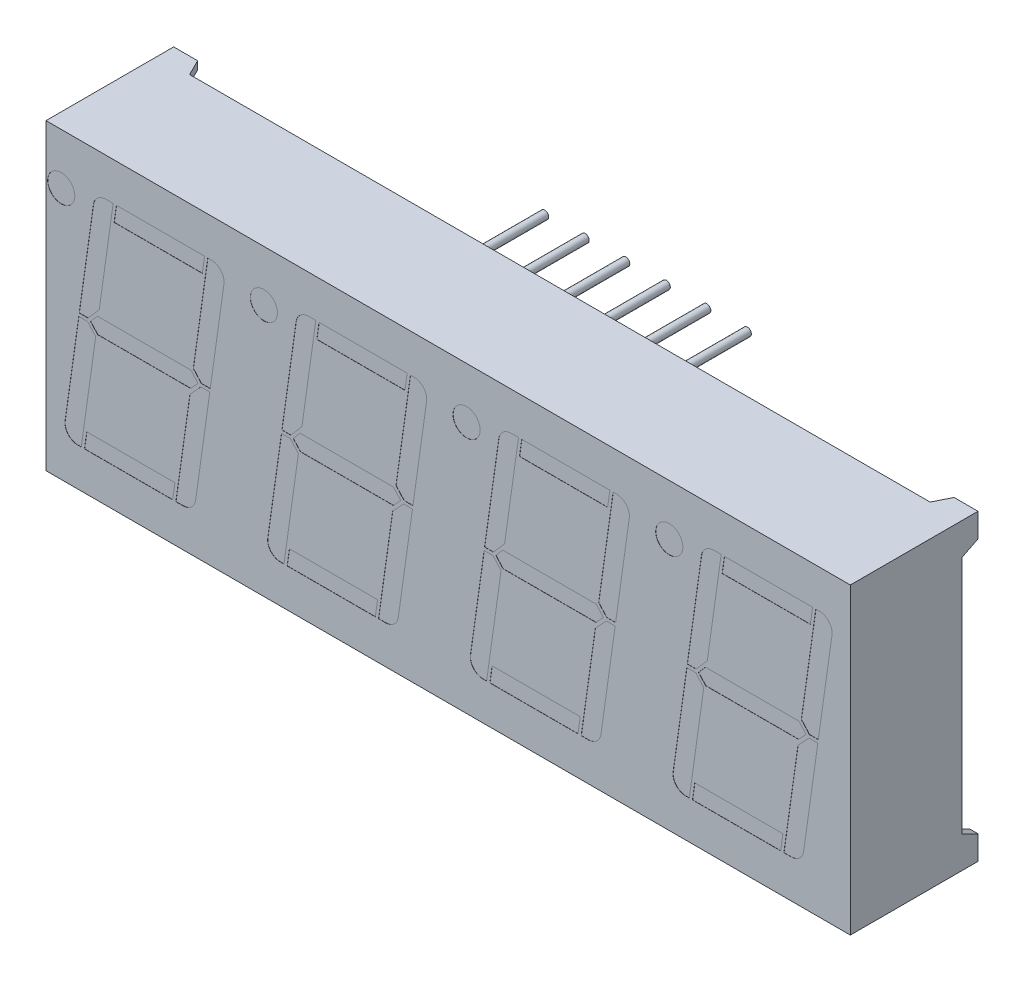
SolidWorks part; units mm, degrees
ref_plane "Front Plane" through (0, 0, 0) normal (0, 0, 1) x (1, 0, 0)
ref_plane "Top Plane" through (0, 0, 0) normal (0, 1, 0) x (1, 0, 0)
ref_plane "Right Plane" through (0, 0, 0) normal (1, 0, 0) x (0, 0, -1)
sketch "Sketch1" plane through (0, 0, 0) normal (0, 1, 0) x (1, 0, 0)
  line L1 (0, 0) -> (50.4, 0)
  line L2 (0, 0) -> (0, 8)
  line L3 (0, 8) -> (50.4, 8)
  line L4 (50.4, 0) -> (50.4, 8)
  dimension "D1" = 8
  dimension "D2" = 50.4
extrude "body" add sketch "Sketch1" along normal blind 19
sketch "Sketch2" plane through (0, 0, -8) normal (0, 0, -1) x (-1, 0, 0)
  line L0 (-50.4, 17) -> (-49.9, 17)
  line L1 (-50.4, 19) -> (-50.4, 0) construction
  line L2 (-49.9, 17) -> (-49.9, 18.5)
  line L3 (-49.9, 18.5) -> (-48.4, 18.5)
  line L4 (-48.4, 18.5) -> (-48.4, 19)
  line L5 (-50.4, 19) -> (0, 19) construction
  line L6 (-48.4, 19) -> (-2, 19)
  line L7 (-2, 19) -> (-2, 18.5)
  line L8 (-2, 18.5) -> (-0.5, 18.5)
  line L9 (-0.5, 18.5) -> (-0.5, 17)
  line L10 (-0.5, 17) -> (0, 17)
  line L11 (0, 19) -> (0, 0) construction
  line L12 (0, 17) -> (0, 2)
  line L13 (0, 2) -> (-0.5, 2)
  line L14 (-0.5, 2) -> (-0.5, 0.5)
  line L15 (-0.5, 0.5) -> (-2, 0.5)
  line L16 (-2, 0.5) -> (-2, 0)
  line L17 (-50.4, 0) -> (0, 0) construction
  line L18 (-2, 0) -> (-48.4, 0)
  line L19 (-48.4, 0) -> (-48.4, 0.5)
  line L20 (-48.4, 0.5) -> (-49.9, 0.5)
  line L21 (-49.9, 0.5) -> (-49.9, 2)
  line L22 (-49.9, 2) -> (-50.4, 2)
  line L23 (-50.4, 2) -> (-50.4, 17)
  line L24 (-49.9, 17) -> (-49.9, 2) construction
  line L25 (-48.4, 0.5) -> (-2, 0.5) construction
  line L26 (-0.5, 2) -> (-0.5, 17) construction
  line L27 (-2, 18.5) -> (-48.4, 18.5) construction
  line L28 (-2, 0.5) -> (-2, 18.5) construction
  line L29 (-0.5, 17) -> (-49.9, 17) construction
  line L30 (-48.4, 0.5) -> (-48.4, 18.5) construction
  line L31 (-49.9, 2) -> (-0.5, 2) construction
  dimension "D1" = 0.5
  dimension "D2" = 2
  dimension "D3" = 2
  dimension "D4" = 2
  dimension "D5" = 2
extrude "backLegs" cut sketch "Sketch2" against normal blind 1
chamfer "backLegsChamfer" distance 0.5 distance2 1 8 edges at (50.15, 2, -8) (48.4, 0.25, -8) (2, 0.25, -8) (0.25, 2, -8) (2, 18.75, -8) (0.25, 17, -8) (48.4, 18.75, -8) (50.15, 17, -8) first distance on face at (49.5667, 0.8333, -8) first distance on face at (0.8333, 0.8333, -8) first distance on face at (0.8333, 18.1667, -8) first distance on face at (49.5667, 18.1667, -8)
sketch "Sketch3" plane through (0, 0, -7) normal (0, 0, -1) x (-1, 0, 0)
  line L21 (-49.9, 0.5) -> (-0.5, 0.5)
  line L22 (-49.9, 0.5) -> (-49.9, 18.5)
  line L23 (-49.9, 18.5) -> (-0.5, 18.5)
  line L24 (-0.5, 0.5) -> (-0.5, 18.5)
extrude "backCut" cut sketch "Sketch3" against normal blind 0.1
sketch "Sketch4" plane through (0, 0, -6.9) normal (0, 0, -1) x (-1, 0, 0)
  line L0 (-49.9, 9.5) -> (-0.5, 9.5) construction
  line L1 (-49.9, 2) -> (-49.9, 17) construction
  line L2 (-0.5, 0.5) -> (-0.5, 18.5) construction
  line L3 (-49.9, 17.12) -> (-0.5, 17.12) construction
  line L4 (-49.9, 18.5) -> (-49.9, 0.5) construction
  line L5 (-0.5, 1.88) -> (-49.9, 1.88) construction
  line L6 (-25.2, 1.88) -> (-25.2, 17.12) construction
  line L7 (-26.47, 17.12) -> (-25.2, 15.85) construction
  line L8 (-25.2, 15.85) -> (-23.93, 17.12) construction
  line L9 (-31.55, 17.12) -> (-31.55, 1.88) construction
  line L10 (-29.01, 17.12) -> (-29.01, 1.88) construction
  line L11 (-26.47, 17.12) -> (-26.47, 1.88) construction
  line L12 (-23.93, 17.12) -> (-23.93, 1.88) construction
  line L13 (-21.39, 17.12) -> (-21.39, 1.88) construction
  line L14 (-18.85, 17.12) -> (-18.85, 1.88) construction
  circle A0 centre (-31.55, 17.12) radius 0.25
  circle A1 centre (-29.01, 17.12) radius 0.25
  circle A2 centre (-26.47, 17.12) radius 0.25
  circle A3 centre (-23.93, 17.12) radius 0.25
  circle A4 centre (-21.39, 17.12) radius 0.25
  circle A5 centre (-18.85, 17.12) radius 0.25
  circle A6 centre (-31.55, 1.88) radius 0.25
  circle A7 centre (-29.01, 1.88) radius 0.25
  circle A8 centre (-26.47, 1.88) radius 0.25
  circle A10 centre (-23.93, 1.88) radius 0.25
  circle A11 centre (-21.39, 1.88) radius 0.25
  circle A12 centre (-18.85, 1.88) radius 0.25
  point P30 (-25.2, 9.5)
  dimension "D6" = 0.5
  dimension "D1" = 15.24
  dimension "D2" = 2.54
  dimension "D3" = 2.54
  dimension "D4" = 2.54
  dimension "D5" = 2.54
  dimension "D7" = 2.54
  dimension "D8" = 45
  dimension "D9" = 45
extrude "pins" add sketch "Sketch4" along normal blind 5.5
sketch "Sketch5" plane through (0, 0, 0) normal (0, 0, 1) x (1, 0, 0)
  line L0 (0, 9.5) -> (50.4, 9.5) construction
  line L1 (0, 19) -> (0, 0) construction
  line L2 (50.4, 19) -> (50.4, 0) construction
  line L3 (49.2488, 15.6987) -> (48.3916, 9.6)
  line L4 (0, 19) -> (50.4, 19) construction
  line L5 (0, 0) -> (50.4, 0) construction
  line L6 (6.15, 19) -> (6.15, 0) construction
  line L7 (18.85, 0) -> (18.85, 19) construction
  line L8 (31.55, 0) -> (31.55, 19) construction
  line L9 (44.25, 0) -> (44.25, 19) construction
  line L10 (25.2, 9.5) -> (25.2, 19) construction
  line L11 (25.2, 14.25) -> (18.85, 14.25) construction
  line L12 (25.2, 14.25) -> (31.55, 14.25) construction
  line L13 (50.4, 16.61) -> (0, 16.61) construction
  line L14 (50.4, 2.39) -> (0, 2.39) construction
  line L15 (49.4, 16.61) -> (49.4, 9.5) construction
  line L16 (49.4, 9.5) -> (49.4, 2.39) construction
  line L17 (48.3916, 9.6) -> (47.8362, 9.6)
  line L18 (47.8362, 9.6) -> (47.3296, 10.1627)
  line L19 (47.3296, 10.1627) -> (48.2357, 16.61)
  line L20 (48.3916, 9.6) -> (48.3635, 9.4) construction
  line L21 (48.3635, 9.4) -> (47.4751, 3.0787)
  line L22 (48.3635, 9.4) -> (47.8081, 9.4)
  line L23 (47.8081, 9.4) -> (47.1185, 8.6605)
  line L24 (47.1185, 8.6605) -> (46.2372, 2.39)
  line L25 (47.6279, 9.5) -> (47.1617, 9)
  line L26 (47.1617, 9) -> (41.3383, 9)
  line L27 (41.3383, 9) -> (40.8881, 9.5)
  line L28 (40.8881, 9.5) -> (41.3223, 10)
  line L29 (41.3223, 10) -> (47.1777, 10)
  line L30 (47.1777, 10) -> (47.6279, 9.5)
  line L31 (44.25, 9) -> (44.25, 10) construction
  line L32 (47.8081, 9.4) -> (47.8362, 9.6) construction
  line L33 (40.709, 9.4) -> (40.7372, 9.6) construction
  line L34 (46.2372, 2.39) -> (46.6829, 2.39)
  line L35 (46.0353, 2.39) -> (46.1758, 3.39)
  line L36 (46.1758, 3.39) -> (40.6521, 3.39)
  line L37 (40.6521, 3.39) -> (40.5115, 2.39)
  line L38 (40.5115, 2.39) -> (46.0353, 2.39)
  line L39 (43.4139, 3.39) -> (43.4139, 2.39) construction
  line L43 (40.1536, 9.4) -> (39.2965, 3.3013)
  line L44 (40.1536, 9.4) -> (40.1818, 9.6) construction
  line L45 (47.3296, 10.1627) -> (47.1185, 8.6605) construction
  line L46 (40.3096, 2.39) -> (41.2157, 8.8373)
  line L47 (40.1818, 9.6) -> (41.0702, 15.9213)
  line L48 (41.436, 10.4048) -> (42.308, 16.61)
  line L49 (41.2157, 8.8373) -> (41.436, 10.4048) construction
  line L50 (41.436, 10.4048) -> (40.7372, 9.6)
  line L51 (40.7372, 9.6) -> (40.1818, 9.6)
  line L52 (44.25, 9.5) -> (44.2005, 9.4505) construction
  line L53 (36.5488, 15.6987) -> (35.6916, 9.6)
  line L54 (41.2157, 8.8373) -> (40.709, 9.4)
  line L55 (40.709, 9.4) -> (40.1536, 9.4)
  line L56 (40.3096, 2.39) -> (40.0887, 2.39)
  line L57 (42.308, 16.61) -> (41.8624, 16.61)
  line L58 (48.2357, 16.61) -> (48.4565, 16.61)
  line L59 (46.1758, 3.39) -> (47.8932, 15.61) construction
  line L60 (40.6521, 3.39) -> (42.3695, 15.61) construction
  line L61 (47.8932, 15.61) -> (42.3695, 15.61)
  line L62 (42.3695, 15.61) -> (42.51, 16.61)
  line L63 (47.8932, 15.61) -> (48.0338, 16.61)
  line L64 (48.0338, 16.61) -> (42.51, 16.61)
  line L65 (35.6916, 9.6) -> (35.1362, 9.6)
  line L66 (35.1362, 9.6) -> (34.6296, 10.1627)
  line L67 (34.6296, 10.1627) -> (35.5357, 16.61)
  line L68 (35.6635, 9.4) -> (34.7751, 3.0787)
  line L69 (35.6635, 9.4) -> (35.1081, 9.4)
  line L70 (35.1081, 9.4) -> (34.4185, 8.6605)
  line L71 (34.4185, 8.6605) -> (33.5372, 2.39)
  line L72 (34.9279, 9.5) -> (34.4617, 9)
  line L73 (34.4617, 9) -> (28.6383, 9)
  line L74 (28.6383, 9) -> (28.1881, 9.5)
  line L75 (28.1881, 9.5) -> (28.6223, 10)
  line L76 (28.6223, 10) -> (34.4777, 10)
  line L77 (34.4777, 10) -> (34.9279, 9.5)
  line L78 (33.5372, 2.39) -> (33.9829, 2.39)
  line L79 (33.3353, 2.39) -> (33.4758, 3.39)
  line L80 (33.4758, 3.39) -> (27.9521, 3.39)
  line L81 (27.9521, 3.39) -> (27.8115, 2.39)
  line L82 (27.8115, 2.39) -> (33.3353, 2.39)
  line L83 (27.4536, 9.4) -> (26.5965, 3.3013)
  line L84 (27.6096, 2.39) -> (28.5157, 8.8373)
  line L85 (27.4818, 9.6) -> (28.3702, 15.9213)
  line L86 (28.736, 10.4048) -> (29.608, 16.61)
  line L87 (28.736, 10.4048) -> (28.0372, 9.6)
  line L88 (28.0372, 9.6) -> (27.4818, 9.6)
  line L89 (28.5157, 8.8373) -> (28.009, 9.4)
  line L90 (28.009, 9.4) -> (27.4536, 9.4)
  line L91 (27.6096, 2.39) -> (27.3887, 2.39)
  line L92 (29.608, 16.61) -> (29.1624, 16.61)
  line L93 (35.5357, 16.61) -> (35.7565, 16.61)
  line L94 (35.1932, 15.61) -> (29.6695, 15.61)
  line L95 (29.6695, 15.61) -> (29.81, 16.61)
  line L96 (35.1932, 15.61) -> (35.3338, 16.61)
  line L97 (35.3338, 16.61) -> (29.81, 16.61)
  line L98 (35.6916, 9.6) -> (35.6635, 9.4) construction
  line L99 (31.55, 9) -> (31.55, 10) construction
  line L100 (35.1081, 9.4) -> (35.1362, 9.6) construction
  line L101 (28.009, 9.4) -> (28.0372, 9.6) construction
  line L102 (30.7139, 3.39) -> (30.7139, 2.39) construction
  line L103 (27.4536, 9.4) -> (27.4818, 9.6) construction
  line L104 (34.6296, 10.1627) -> (34.4185, 8.6605) construction
  line L105 (28.5157, 8.8373) -> (28.736, 10.4048) construction
  line L106 (31.55, 9.5) -> (31.5005, 9.4505) construction
  line L107 (33.4758, 3.39) -> (35.1932, 15.61) construction
  line L108 (27.9521, 3.39) -> (29.6695, 15.61) construction
  line L109 (23.8488, 15.6987) -> (22.9916, 9.6)
  line L110 (22.9916, 9.6) -> (22.4362, 9.6)
  line L111 (22.4362, 9.6) -> (21.9296, 10.1627)
  line L112 (21.9296, 10.1627) -> (22.8357, 16.61)
  line L113 (22.9635, 9.4) -> (22.0751, 3.0787)
  line L114 (22.9635, 9.4) -> (22.4081, 9.4)
  line L115 (22.4081, 9.4) -> (21.7185, 8.6605)
  line L116 (21.7185, 8.6605) -> (20.8372, 2.39)
  line L117 (22.2279, 9.5) -> (21.7617, 9)
  line L118 (21.7617, 9) -> (15.9383, 9)
  line L119 (15.9383, 9) -> (15.4881, 9.5)
  line L120 (15.4881, 9.5) -> (15.9223, 10)
  line L121 (15.9223, 10) -> (21.7777, 10)
  line L122 (21.7777, 10) -> (22.2279, 9.5)
  line L123 (20.8372, 2.39) -> (21.2829, 2.39)
  line L124 (20.6353, 2.39) -> (20.7758, 3.39)
  line L125 (20.7758, 3.39) -> (15.2521, 3.39)
  line L126 (15.2521, 3.39) -> (15.1115, 2.39)
  line L127 (15.1115, 2.39) -> (20.6353, 2.39)
  line L128 (14.7536, 9.4) -> (13.8965, 3.3013)
  line L129 (14.9096, 2.39) -> (15.8157, 8.8373)
  line L130 (14.7818, 9.6) -> (15.6702, 15.9213)
  line L131 (16.036, 10.4048) -> (16.908, 16.61)
  line L132 (16.036, 10.4048) -> (15.3372, 9.6)
  line L133 (15.3372, 9.6) -> (14.7818, 9.6)
  line L134 (15.8157, 8.8373) -> (15.309, 9.4)
  line L135 (15.309, 9.4) -> (14.7536, 9.4)
  line L136 (14.9096, 2.39) -> (14.6887, 2.39)
  line L137 (16.908, 16.61) -> (16.4624, 16.61)
  line L138 (22.8357, 16.61) -> (23.0565, 16.61)
  line L139 (22.4932, 15.61) -> (16.9695, 15.61)
  line L140 (16.9695, 15.61) -> (17.11, 16.61)
  line L141 (22.4932, 15.61) -> (22.6338, 16.61)
  line L142 (22.6338, 16.61) -> (17.11, 16.61)
  line L143 (22.9916, 9.6) -> (22.9635, 9.4) construction
  line L144 (18.85, 9) -> (18.85, 10) construction
  line L145 (22.4081, 9.4) -> (22.4362, 9.6) construction
  line L146 (15.309, 9.4) -> (15.3372, 9.6) construction
  line L147 (18.0139, 3.39) -> (18.0139, 2.39) construction
  line L148 (14.7536, 9.4) -> (14.7818, 9.6) construction
  line L149 (21.9296, 10.1627) -> (21.7185, 8.6605) construction
  line L150 (15.8157, 8.8373) -> (16.036, 10.4048) construction
  line L151 (18.85, 9.5) -> (18.8005, 9.4505) construction
  line L152 (20.7758, 3.39) -> (22.4932, 15.61) construction
  line L153 (15.2521, 3.39) -> (16.9695, 15.61) construction
  line L154 (11.1488, 15.6987) -> (10.2916, 9.6)
  line L155 (10.2916, 9.6) -> (9.7362, 9.6)
  line L156 (9.7362, 9.6) -> (9.2296, 10.1627)
  line L157 (9.2296, 10.1627) -> (10.1357, 16.61)
  line L158 (10.2635, 9.4) -> (9.3751, 3.0787)
  line L159 (10.2635, 9.4) -> (9.7081, 9.4)
  line L160 (9.7081, 9.4) -> (9.0185, 8.6605)
  line L161 (9.0185, 8.6605) -> (8.1372, 2.39)
  line L162 (9.5279, 9.5) -> (9.0617, 9)
  line L163 (9.0617, 9) -> (3.2383, 9)
  line L164 (3.2383, 9) -> (2.7881, 9.5)
  line L165 (2.7881, 9.5) -> (3.2223, 10)
  line L166 (3.2223, 10) -> (9.0777, 10)
  line L167 (9.0777, 10) -> (9.5279, 9.5)
  line L168 (8.1372, 2.39) -> (8.5829, 2.39)
  line L169 (7.9353, 2.39) -> (8.0758, 3.39)
  line L170 (8.0758, 3.39) -> (2.5521, 3.39)
  line L171 (2.5521, 3.39) -> (2.4115, 2.39)
  line L172 (2.4115, 2.39) -> (7.9353, 2.39)
  line L173 (2.0536, 9.4) -> (1.1965, 3.3013)
  line L174 (2.2096, 2.39) -> (3.1157, 8.8373)
  line L175 (2.0818, 9.6) -> (2.9702, 15.9213)
  line L176 (3.336, 10.4048) -> (4.208, 16.61)
  line L177 (3.336, 10.4048) -> (2.6372, 9.6)
  line L178 (2.6372, 9.6) -> (2.0818, 9.6)
  line L179 (3.1157, 8.8373) -> (2.609, 9.4)
  line L180 (2.609, 9.4) -> (2.0536, 9.4)
  line L181 (2.2096, 2.39) -> (1.9887, 2.39)
  line L182 (4.208, 16.61) -> (3.7624, 16.61)
  line L183 (10.1357, 16.61) -> (10.3565, 16.61)
  line L184 (9.7932, 15.61) -> (4.2695, 15.61)
  line L185 (4.2695, 15.61) -> (4.41, 16.61)
  line L186 (9.7932, 15.61) -> (9.9338, 16.61)
  line L187 (9.9338, 16.61) -> (4.41, 16.61)
  line L188 (10.2916, 9.6) -> (10.2635, 9.4) construction
  line L189 (6.15, 9) -> (6.15, 10) construction
  line L190 (9.7081, 9.4) -> (9.7362, 9.6) construction
  line L191 (2.609, 9.4) -> (2.6372, 9.6) construction
  line L192 (5.3139, 3.39) -> (5.3139, 2.39) construction
  line L193 (2.0536, 9.4) -> (2.0818, 9.6) construction
  line L194 (9.2296, 10.1627) -> (9.0185, 8.6605) construction
  line L195 (3.1157, 8.8373) -> (3.336, 10.4048) construction
  line L196 (6.15, 9.5) -> (6.1005, 9.4505) construction
  line L197 (8.0758, 3.39) -> (9.7932, 15.61) construction
  line L198 (2.5521, 3.39) -> (4.2695, 15.61) construction
  line L199 (39.0545, 16.61) -> (39.0545, 15.81) construction
  line L200 (39.0545, 15.81) -> (41.0545, 15.81) construction
  line L201 (26.3545, 15.81) -> (28.3545, 15.81) construction
  line L202 (26.3545, 15.81) -> (26.3545, 16.61) construction
  arc A0 (48.4565, 16.61) -> (49.2488, 15.6987) centre (48.4565, 15.81) cw
  arc A2 (47.4751, 3.0787) -> (46.6829, 2.39) centre (46.6829, 3.19) cw
  arc A3 (39.2965, 3.3013) -> (40.0887, 2.39) centre (40.0887, 3.19) ccw
  arc A4 (41.8624, 16.61) -> (41.0702, 15.9213) centre (41.8624, 15.81) ccw
  arc A5 (35.7565, 16.61) -> (36.5488, 15.6987) centre (35.7565, 15.81) cw
  arc A6 (34.7751, 3.0787) -> (33.9829, 2.39) centre (33.9829, 3.19) cw
  arc A7 (26.5965, 3.3013) -> (27.3887, 2.39) centre (27.3887, 3.19) ccw
  arc A8 (29.1624, 16.61) -> (28.3702, 15.9213) centre (29.1624, 15.81) ccw
  arc A9 (23.0565, 16.61) -> (23.8488, 15.6987) centre (23.0565, 15.81) cw
  arc A10 (22.0751, 3.0787) -> (21.2829, 2.39) centre (21.2829, 3.19) cw
  arc A11 (13.8965, 3.3013) -> (14.6887, 2.39) centre (14.6887, 3.19) ccw
  arc A12 (16.4624, 16.61) -> (15.6702, 15.9213) centre (16.4624, 15.81) ccw
  arc A13 (10.3565, 16.61) -> (11.1488, 15.6987) centre (10.3565, 15.81) cw
  arc A14 (9.3751, 3.0787) -> (8.5829, 2.39) centre (8.5829, 3.19) cw
  arc A15 (1.1965, 3.3013) -> (1.9887, 2.39) centre (1.9887, 3.19) ccw
  arc A16 (3.7624, 16.61) -> (2.9702, 15.9213) centre (3.7624, 15.81) ccw
  circle A17 centre (39.0545, 15.81) radius 0.85
  circle A18 centre (26.3545, 15.81) radius 0.85
  circle A19 centre (13.6545, 15.81) radius 0.85
  circle A20 centre (0.9545, 15.81) radius 0.85
  point P36 (48.3776, 9.5)
  point P51 (44.25, 9.5)
  point P66 (43.4139, 3.39)
  point P67 (40.1677, 9.5)
  dimension "D8" = 1.13
  dimension "D10" = 0.8
  dimension "D20" = 0.8
  dimension "D24" = 1.13
  dimension "D23" = 1.13
  dimension "D13" = 0.8
  dimension "D22" = 0.8
  dimension "D32" = 1.7
  dimension "D1" = 12.7
  dimension "D2" = 12.7
  dimension "D3" = 12.7
  dimension "D4" = 14.22
  dimension "D5" = 1
  dimension "D6" = 8
  dimension "D7" = 0.55
  dimension "D9" = 0.55
  dimension "D11" = 0.1
  dimension "D12" = 1
  dimension "D14" = 1
  dimension "D15" = 0.2
  dimension "D16" = 0.1
  dimension "D17" = 0.2
  dimension "D18" = 8.13
  dimension "D19" = 130
  dimension "D21" = 145
  dimension "D25" = 1.13
  dimension "D26" = 130
  dimension "D27" = 0.2
  dimension "D28" = 0.2
  dimension "D30" = 0.8
  dimension "D31" = 2
  dimension "D34" = 2
  dimension "D29" = 4
  dimension "D33" = 4
extrude "display" cut sketch "Sketch5" against normal blind 0.01
